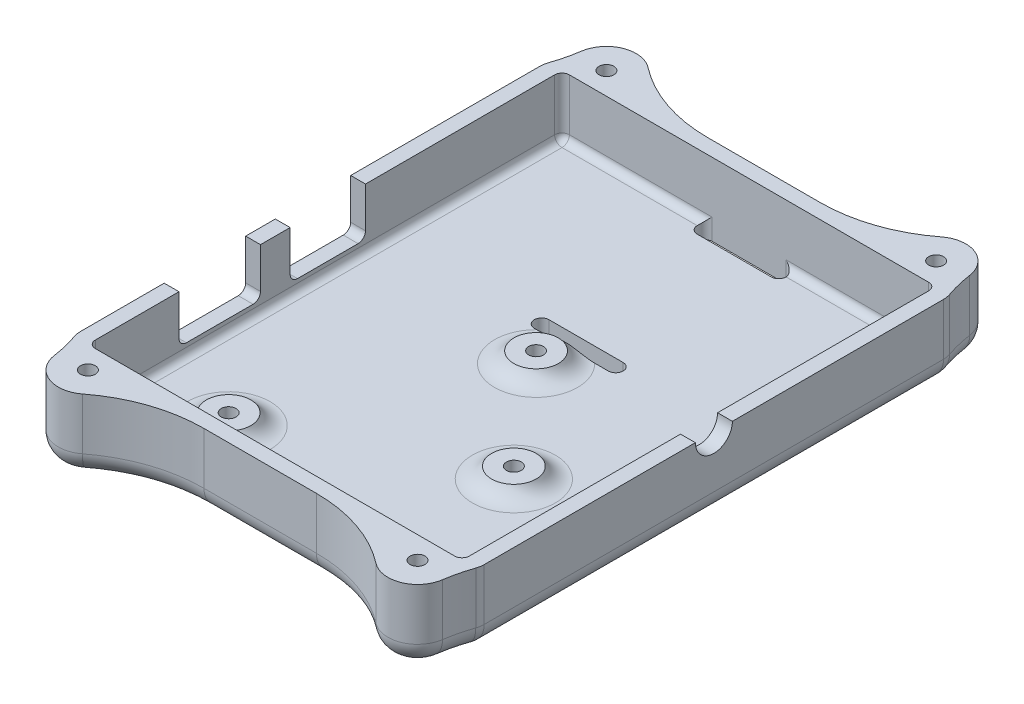
SolidWorks part; units mm, degrees
ref_plane "Front Plane" through (0, 0, 0) normal (0, 0, 1) x (1, 0, 0)
ref_plane "Top Plane" through (0, 0, 0) normal (0, 1, 0) x (1, 0, 0)
ref_plane "Right Plane" through (0, 0, 0) normal (1, 0, 0) x (0, 0, -1)
sketch "Sketch1" plane through (0, 0, 0) normal (0, 1, 0) x (1, 0, 0)
  line L0 (-16.25, 20) -> (-6.25, 20) construction
  line L1 (-34.5, 17.5) -> (12, 17.5) construction
  line L2 (-34.5, 17.5) -> (-34.5, -20) construction
  line L3 (-34.5, -20) -> (12, -20) construction
  line L4 (12, 17.5) -> (12, -20) construction
  line L5 (-28.5, 39.5) -> (6, 39.5) construction
  line L6 (-28.5, 39.5) -> (-28.5, 22.5) construction
  line L7 (-28.5, 22.5) -> (6, 22.5) construction
  line L8 (6, 39.5) -> (6, 22.5) construction
  line L9 (-35.5, 45) -> (13, 45)
  line L10 (-38.5, 42) -> (-38.5, -20)
  line L11 (-35.5, -23) -> (13, -23)
  line L12 (16, 42) -> (16, -20)
  line L13 (-16.25, 21) -> (-6.25, 21)
  line L14 (-16.25, 19) -> (-6.25, 19)
  line L15 (-16.25, 42) -> (-6.25, 42) construction
  line L16 (-16.25, 43) -> (-6.25, 43)
  line L17 (-16.25, 41) -> (-6.25, 41)
  circle A0 centre (-25.5, -13) radius 1
  circle A1 centre (0, 0) radius 1
  circle A2 centre (-12, 15) radius 1
  arc A6 (13, 45) -> (16, 42) centre (13, 42) cw
  arc A7 (13, -23) -> (16, -20) centre (13, -20) ccw
  arc A8 (-38.5, -20) -> (-35.5, -23) centre (-35.5, -20) ccw
  arc A9 (-35.5, 45) -> (-38.5, 42) centre (-35.5, 42) ccw
  arc A10 (-16.25, 21) -> (-16.25, 19) centre (-16.25, 20) ccw
  arc A11 (-6.25, 19) -> (-6.25, 21) centre (-6.25, 20) ccw
  arc A12 (-16.25, 43) -> (-16.25, 41) centre (-16.25, 42) ccw
  arc A13 (-6.25, 41) -> (-6.25, 43) centre (-6.25, 42) ccw
  point P9 (-11.25, 20)
  point P12 (-11.25, -23)
  point P18 (-11.25, 39.5)
  point P23 (-11.25, -20)
  point P37 (-11.25, 42)
  point P38 (-11.25, 22.5)
  point P45 (0, 0)
  point P46 (0, 0)
  dimension "D1" = 2
  dimension "D16" = 3
  dimension "D18" = 1
  dimension "D2" = 25.5
  dimension "D3" = 13
  dimension "D4" = 12
  dimension "D5" = 15
  dimension "D7" = 9
  dimension "D8" = 7
  dimension "D9" = 2.5
  dimension "D10" = 12
  dimension "D11" = 34.5
  dimension "D12" = 17
  dimension "D13" = 5
  dimension "D6" = 4
  dimension "D14" = 3
  dimension "D15" = 5.5
  dimension "D17" = 10
  dimension "D19" = 2.5
  dimension "D20" = 2.5
extrude "Casing bottom" add sketch "Sketch1" along normal blind 2
sketch "Sketch2" plane through (0, 2, 0) normal (0, 1, 0) x (1, 0, 0)
  line L0 (-36.5, 42) -> (-36.5, -20)
  line L1 (-35.5, -21) -> (13, -21)
  line L2 (14, -20) -> (14, 42)
  line L3 (13, 43) -> (-35.5, 43)
  line L4 (-38.5, 42) -> (-38.5, -20)
  line L5 (-35.5, -23) -> (13, -23)
  line L6 (16, -20) -> (16, 42)
  line L7 (13, 45) -> (-35.5, 45)
  line L8 (-38.5, 42) -> (-38.5, -20)
  line L9 (-35.5, -23) -> (13, -23)
  line L10 (16, -20) -> (16, 42)
  line L11 (13, 45) -> (-35.5, 45)
  line L12 (-36.5, -21) -> (14, -21) construction
  line L13 (14, -21) -> (14, 43) construction
  line L14 (14, 43) -> (-36.5, 43) construction
  line L15 (-36.5, 43) -> (-36.5, -21) construction
  line L16 (16, -23) -> (16, 45) construction
  line L17 (16, 45) -> (-38.5, 45) construction
  line L18 (-38.5, -23) -> (16, -23) construction
  line L19 (-38.5, 45) -> (-38.5, -23) construction
  arc A0 (13, -21) -> (14, -20) centre (13, -20) ccw
  arc A1 (14, 42) -> (13, 43) centre (13, 42) ccw
  arc A2 (-36.5, 42) -> (-35.5, 43) centre (-35.5, 42) cw
  arc A3 (-36.5, -20) -> (-35.5, -21) centre (-35.5, -20) ccw
  arc A4 (16, 42) -> (13, 45) centre (13, 42) ccw
  arc A5 (13, -23) -> (16, -20) centre (13, -20) ccw
  arc A6 (-38.5, -20) -> (-35.5, -23) centre (-35.5, -20) ccw
  arc A7 (-38.5, 42) -> (-35.5, 45) centre (-35.5, 42) cw
  arc A12 (16, 42) -> (13, 45) centre (13, 42) ccw
  arc A13 (16, 42) -> (13, 45) centre (13, 42) ccw
  arc A14 (-35.5, 45) -> (-38.5, 42) centre (-35.5, 42) ccw
  arc A15 (-35.5, 45) -> (-38.5, 42) centre (-35.5, 42) ccw
  arc A16 (-38.5, -20) -> (-35.5, -23) centre (-35.5, -20) ccw
  arc A17 (-38.5, -20) -> (-35.5, -23) centre (-35.5, -20) ccw
  arc A18 (13, -23) -> (16, -20) centre (13, -20) ccw
  arc A19 (13, -23) -> (16, -20) centre (13, -20) ccw
  line M10 (-38.5, 42) -> (-38.5, -20)
  line M11 (-35.5, -23) -> (13, -23)
  line M12 (16, -20) -> (16, 42)
  line M13 (13, 45) -> (-35.5, 45)
  arc M24 (16, 42) -> (13, 45) centre (13, 42) ccw
  arc M25 (-35.5, 45) -> (-38.5, 42) centre (-35.5, 42) ccw
  arc M26 (-38.5, -20) -> (-35.5, -23) centre (-35.5, -20) ccw
  arc M27 (13, -23) -> (16, -20) centre (13, -20) ccw
  dimension "D3" = 1
  dimension "D4" = 3
  dimension "D1" = 0
  dimension "D2" = 2
extrude "Casing walls" add sketch "Sketch2" along normal blind 8 contours A3 L0 A2 L3 A1 L2 A0 L1 M12 M24 M13 M25 M10 M26 M11 M27 region at (-37.0051, 2, -43.5051)
fillet "Fillet1" radius 1 9 edges at (-25.875, 2, -43) (-36.2071, 2, -42.7071) (-36.5, 2, -11) (-36.2071, 2, 20.7071) (3.375, 2, -43) (13.7071, 2, -42.7071) (14, 2, -11) (13.7071, 2, 20.7071) (-11.25, 2, 21)
sketch "Sketch3" plane through (0, 10, 0) normal (0, 1, 0) x (1, 0, 0)
  line L0 (13, 45) -> (-35.5, 45) construction
  line L1 (-38.5, 42) -> (-38.5, -20) construction
  line L2 (16, -20) -> (16, 42) construction
  line L3 (-35.5, 43) -> (-16.25, 43) construction
  line L4 (-35.5, 43) -> (-30.8542, 43)
  line L5 (-6.25, 43) -> (13, 43) construction
  line L6 (8.3542, 43) -> (13, 43)
  line L7 (-38.5, 11) -> (16, 11) construction
  line L8 (8.3542, -21) -> (13, -21)
  line L9 (-35.5, -21) -> (-30.8542, -21)
  circle A0 centre (-33.5, 46) radius 1
  circle A1 centre (11, 46) radius 1
  arc A2 (-30.8542, 43) -> (-35.9916, 42.8708) centre (-33.5, 46) ccw
  arc A3 (13.4916, 42.8708) -> (8.3542, 43) centre (11, 46) ccw
  arc A4 (-35.5, 43) -> (-36.5, 42) centre (-35.5, 42) ccw construction
  arc A5 (-35.5, 43) -> (-35.9916, 42.8708) centre (-35.5, 42) ccw
  arc A6 (14, 42) -> (13, 43) centre (13, 42) ccw construction
  arc A7 (13.4916, 42.8708) -> (13, 43) centre (13, 42) ccw
  circle A8 centre (11, 46) radius 4 construction
  circle A9 centre (-33.5, 46) radius 4 construction
  arc A10 (13.4916, -20.8708) -> (13, -21) centre (13, -20) cw
  arc A11 (-35.5, -21) -> (-35.9916, -20.8708) centre (-35.5, -20) cw
  arc A12 (13.4916, -20.8708) -> (8.3542, -21) centre (11, -24) cw
  arc A13 (-30.8542, -21) -> (-35.9916, -20.8708) centre (-33.5, -24) cw
  circle A14 centre (11, -24) radius 1
  circle A15 centre (-33.5, -24) radius 1
  dimension "D3" = 2
  dimension "D1" = 5
  dimension "D2" = 5
  dimension "D4" = 3
extrude "Boss-Extrude3" add sketch "Sketch3" against normal up to surface (10 mm away) up to face at (0, 0, 1)
fillet "Fillet2" radius 20 8 edges at (14.6973, 5, -44.4737) (14.6973, 5, 22.4737) (-37.1973, 5, 22.4737) (-37.1973, 5, -44.4737) (-29.627, 5, 23) (7.127, 5, 23) (7.127, 5, -45) (-29.627, 5, -45)
fillet "Fillet3" radius 3 20 edges at (-25.2921, 0, 24.0703) (-34.9972, 0, 27.7092) (-37.813, 0, 22.7599) (-38.4588, 0, 20.4957) (-38.5, 0, -11) (-38.4588, 0, -42.4957) (-37.813, 0, -44.7599) (-34.9972, 0, -49.7092) (-25.2921, 0, -46.0703) (-11.25, 0, -45) (2.7921, 0, -46.0703) (12.4972, 0, -49.7092) (15.313, 0, -44.7599) (15.9588, 0, -42.4957) (16, 0, -11) (15.9588, 0, 20.4957) (15.313, 0, 22.7599) (12.4972, 0, 27.7092) (2.7921, 0, 24.0703) (-11.25, 0, 23)
sketch "Sketch5" plane through (0, 2, 0) normal (0, 1, 0) x (1, 0, 0)
  circle A0 centre (-25.5, -13) radius 1 construction
  circle A1 centre (0, 0) radius 1 construction
  circle A2 centre (-25.5, -13) radius 1
  circle A3 centre (0, 0) radius 1
  circle A4 centre (-12, 15) radius 1 construction
  circle A5 centre (-12, 15) radius 1
  circle A6 centre (-25.5, -13) radius 3
  circle A7 centre (0, 0) radius 3
  circle A8 centre (-12, 15) radius 3
  dimension "D1" = 2
extrude "Boss-Extrude4" add sketch "Sketch5" along normal blind 1.5
fillet "Fillet4" radius 3 3 edges at (-25.5, 2, 10) (0, 2, -3) (-12, 2, -18)
sketch "Sketch6" plane through (-38.5, 0, 0) normal (-1, 0, 0) x (0, 0, 1)
  line L0 (-6.299, 11.5315) -> (-6.299, 9.4515) construction
  line L1 (-16.473, 11.5315) -> (-6.299, 11.5315)
  line L2 (-16.473, 11.5315) -> (-16.473, 3.5315)
  line L3 (-16.473, 3.5315) -> (-6.299, 3.5315)
  line L4 (-6.299, 11.5315) -> (-6.299, 3.5315)
  line L5 (-42, 10) -> (20, 10) construction
  line L6 (-2.299, 10) -> (8.701, 10)
  line L7 (-2.299, 10) -> (-2.299, 3.5315)
  line L8 (-2.299, 3.5315) -> (8.701, 3.5315)
  line L9 (8.701, 10) -> (8.701, 3.5315)
  dimension "D1" = 8
  dimension "D2" = 4
  dimension "D3" = 11
extrude "Cut-Extrude2" cut sketch "Sketch6" against normal blind 2
fillet "Fillet5" radius 1 4 edges at (-37.5, 3.5315, 8.701) (-37.5, 3.5315, -2.299) (-37.5, 3.5315, -16.473) (-37.5, 3.5315, -6.299)
sketch "Sketch7" plane through (16, 0, 0) normal (1, 0, 0) x (0, 0, -1)
  line L0 (8.5, 10) -> (13.5, 10)
  line L1 (-20, 10) -> (42, 10) construction
  arc A0 (8.5, 10) -> (13.5, 10) centre (11, 10) ccw
  point P5 (11, 10)
  dimension "D1" = 2.5
extrude "Cut-Extrude3" cut sketch "Sketch7" against normal blind 2
